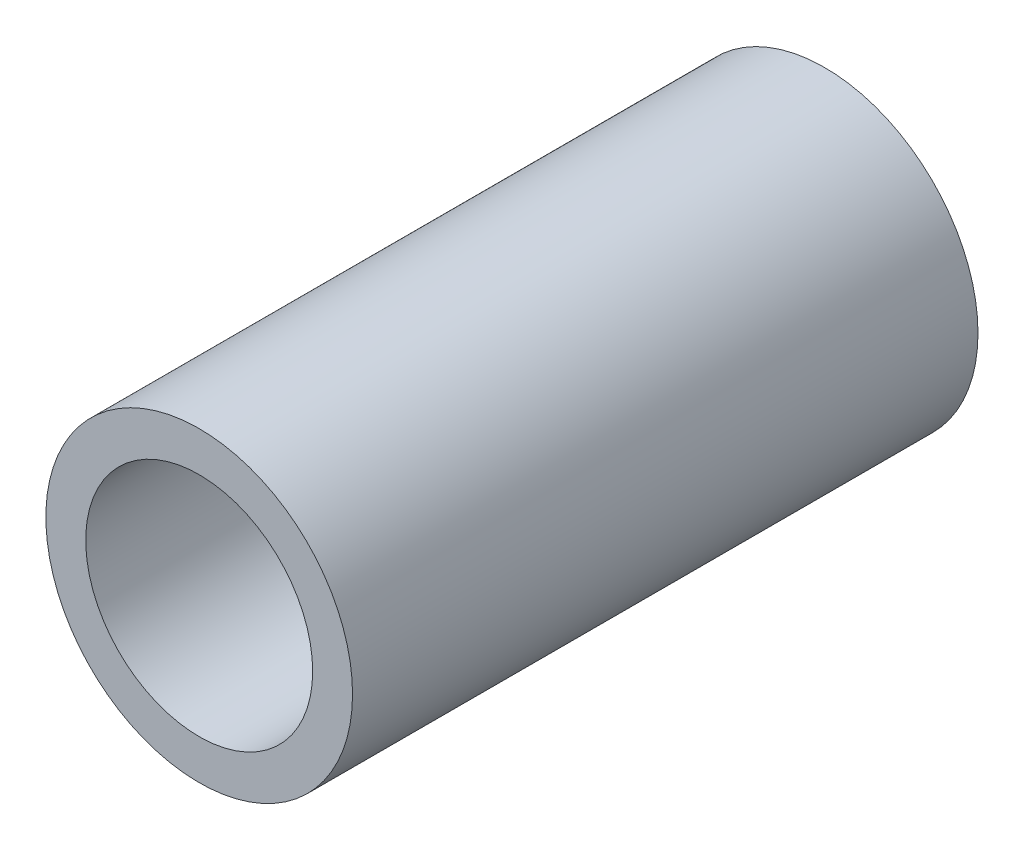
SolidWorks part; units mm, degrees
ref_plane "Front Plane" through (0, 0, 0) normal (0, 0, 1) x (1, 0, 0)
ref_plane "Top Plane" through (0, 0, 0) normal (0, 1, 0) x (1, 0, 0)
ref_plane "Right Plane" through (0, 0, 0) normal (1, 0, 0) x (0, 0, -1)
sketch "Sketch1" plane through (0, 0, 0) normal (0, 0, 1) x (1, 0, 0)
  circle A0 centre (0, 0) radius 4.699
  circle A1 centre (0, 0) radius 6.35
  dimension "D1" = 12.7
  dimension "D2" = 9.398
extrude "Boss-Extrude1" add sketch "Sketch1" along normal up to surface (25.9 mm away)
